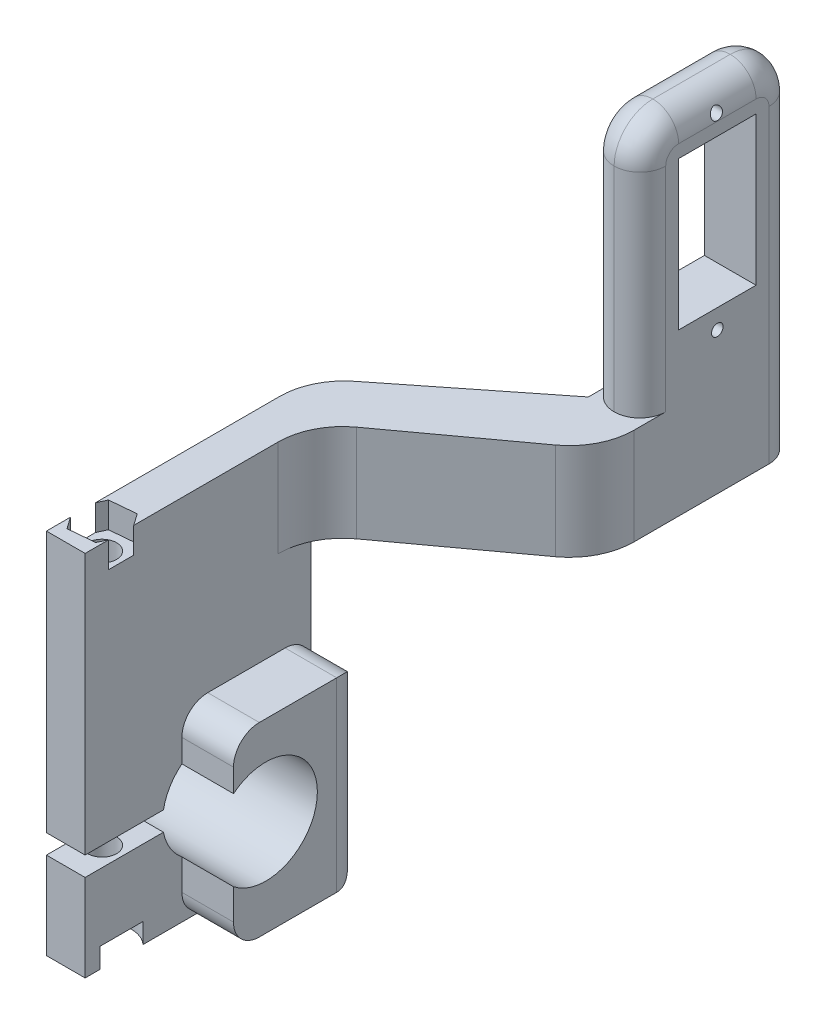
SolidWorks part; units mm, degrees
ref_plane "Front Plane" through (0, 0, 0) normal (0, 0, 1) x (1, 0, 0)
ref_plane "Top Plane" through (0, 0, 0) normal (0, 1, 0) x (1, 0, 0)
ref_plane "Right Plane" through (0, 0, 0) normal (1, 0, 0) x (0, 0, -1)
sketch "Sketch1" plane through (0, 0, 0) normal (1, 0, 0) x (0, 0, -1)
  line L0 (-55.3503, -42.4114) -> (-43.2084, -42.4114)
  line L2 (4.6497, -1.9114) -> (4.6497, 37.0886)
  line L3 (4.6497, 37.0886) -> (28.6497, 37.0886)
  line L4 (10.6497, 31.0886) -> (22.6497, 31.0886)
  line L5 (-27.3711, -35.4334) -> (28.6497, 37.0886) construction
  line L6 (4.6497, 37.0886) -> (-5.2585, -41.9446) construction
  line L7 (-20.3503, -58.9114) -> (-55.3503, -58.9114)
  line L8 (-55.3503, -45.4114) -> (-43.2084, -45.4114)
  line L10 (-55.3503, -58.9114) -> (-55.3503, -45.4114)
  line L11 (10.6497, 31.0886) -> (10.6497, 8.0886)
  line L12 (28.6497, 37.0886) -> (28.6497, -16.9114)
  line L13 (10.6497, 8.0886) -> (22.6497, 8.0886)
  line L14 (22.6497, 31.0886) -> (22.6497, 8.0886)
  line L15 (-55.3503, -42.4114) -> (-55.3503, -28.9114)
  line L18 (28.6497, -16.9114) -> (-20.3503, -16.9114)
  line L19 (4.6497, -1.9114) -> (-55.3503, -1.9114)
  line L20 (-55.3503, -28.9114) -> (-55.3503, -1.9114)
  line L21 (-20.3503, -58.9114) -> (-20.3503, -16.9114)
  arc A0 (-43.2084, -45.4114) -> (-43.2084, -42.4114) centre (-35.3503, -43.9114) ccw
  circle A1 centre (16.6497, 34.0886) radius 0.9
  circle A2 centre (16.6497, 5.0886) radius 0.9
  point P0 (0, 0)
  dimension "D3" = 16
  dimension "D11" = 1.8
  dimension "D12" = 1.8
  dimension "D1" = 30
  dimension "D2" = 15
  dimension "D4" = 35
  dimension "D5" = 20
  dimension "D6" = 24
  dimension "D7" = 12
  dimension "D8" = 6
  dimension "D9" = 6
  dimension "D10" = 23
  dimension "D13" = 3
  dimension "D14" = 3
  dimension "D15" = 6
  dimension "D16" = 6
  dimension "D17" = 13.5
  dimension "D18" = 3
  dimension "D19" = 86
  dimension "D20" = 25
  dimension "D21" = 42
  dimension "D22" = 60
extrude "Boss-Extrude1" add sketch "Sketch1" along normal blind 32
hole_wizard "CBORE for M4 Pan Head Machine Screw2" positions "Sketch6" profile "Sketch5" counterbore size "M4" standard "ANSI Metric" end condition through all
sketch "Sketch6" plane through (0, -58.9114, 0) normal (0, -1, 0) x (-1, 0, 0)
  line L0 (-32, -55.3503) -> (0, -55.3503) construction
  line L1 (0, -55.3503) -> (0, -20.3503) construction
  point P0 (-3, -49.7203)
  dimension "D1" = 5.63
  dimension "D2" = 3
sketch "Sketch5" plane through (3, -58.9114, 49.7203) normal (1, 0, 0) x (0, 0, -1)
  line L0 (0, 0) -> (0, 96)
  line L1 (0, 96) -> (2.25, 96)
  line L3 (2.25, 96) -> (2.25, 3.1)
  line L4 (2.25, 3.1) -> (4.5, 3.1)
  line L5 (4.5, 3.1) -> (4.5, 0)
  line L7 (4.5, 0) -> (0, 0)
  line L11 (0, -6.35) -> (0, 107.95) construction
  dimension "Thru Hole Dia." = 4.5
  dimension "Thru Hole Depth" = 96
  dimension "C'Bore Dia." = 9
  dimension "C'Bore Depth" = 3.1
sketch "Sketch7" plane through (0, -1.9114, 0) normal (0, 1, 0) x (1, 0, 0)
  line L1 (7.0823, -49.3481) -> (4.7188, -45.9989)
  line L2 (4.7188, -45.9989) -> (0.6365, -46.3711)
  line L3 (0.6365, -46.3711) -> (-1.0823, -50.0925)
  line L4 (-1.0823, -50.0925) -> (1.2812, -53.4417)
  line L5 (1.2812, -53.4417) -> (5.3635, -53.0695)
  line L6 (5.3635, -53.0695) -> (7.0823, -49.3481)
  circle A0 centre (3, -49.7203) radius 3.55 construction
  dimension "D1" = 7.1
extrude "Cut-Extrude2" cut sketch "Sketch7" against normal blind 4
sketch "Sketch9" plane through (32, 0, 0) normal (1, 0, 0) x (0, 0, -1)
  line L0 (4.6497, -1.9114) -> (-55.3503, -1.9114) construction
  line L1 (-55.3503, -58.9114) -> (-20.3503, -58.9114)
  line L2 (-55.3503, -58.9114) -> (-55.3503, -1.9114)
  line L3 (-55.3503, -1.9114) -> (-20.3503, -1.9114)
  line L4 (-20.3503, -58.9114) -> (-20.3503, -1.9114)
  line L5 (-20.3503, -58.9114) -> (-20.3503, -16.9114) construction
  dimension "D1" = 0
extrude "Cut-Extrude3" cut sketch "Sketch9" against normal blind 26
sketch "Sketch10" plane through (0, 0, 0) normal (-1, 0, 0) x (0, 0, 1)
  line L1 (-28.6497, -16.9114) -> (-4.6497, -16.9114)
  line L2 (-28.6497, -16.9114) -> (-28.6497, 37.0886)
  line L3 (-28.6497, 37.0886) -> (-4.6497, 37.0886)
  line L4 (-4.6497, -16.9114) -> (-4.6497, 37.0886)
extrude "Cut-Extrude4" cut sketch "Sketch10" against normal blind 24
sketch "Sketch11" plane through (0, 0, 0) normal (-1, 0, 0) x (0, 0, 1)
  line L0 (20.3503, -30.1091) -> (40.3503, -30.1091)
  line L1 (20.3503, -58.9114) -> (20.3503, -16.9114) construction
  line L2 (40.3503, -30.1091) -> (40.3503, -37.6664)
  line L3 (40.3503, -50.1564) -> (40.3503, -58.9114)
  line L4 (46.3662, -58.9114) -> (20.3503, -58.9114) construction
  line L5 (40.3503, -58.9114) -> (20.3503, -58.9114)
  line L6 (20.3503, -58.9114) -> (20.3503, -30.1091)
  arc A0 (40.3503, -37.6664) -> (40.3503, -50.1564) centre (35.3503, -43.9114) ccw
  dimension "D2" = 8
  dimension "D1" = 20
extrude "Boss-Extrude2" add sketch "Sketch11" along normal blind 8 and the other way blind 14
fillet "Fillet3" radius 4 9 edges at (10, -58.9114, 40.3503) (10, -30.1091, 40.3503) (-4, -58.9114, 40.3503) (-4, -30.1091, 40.3503) (10, -30.1091, 20.3503) (14, -44.5103, 20.3503) (3, -58.9114, 20.3503) (-8, -44.5103, 20.3503) (-4, -30.1091, 20.3503)
fillet "Fillet4" radius 6 2 edges at (28, 37.0886, -4.6497) (28, 37.0886, -28.6497)
fillet "Fillet5" radius 4 10 edges at (32, 14.5886, -4.6497) (32, 35.3312, -6.4071) (32, 37.0886, -16.6497) (32, 35.3312, -26.8923) (24, 14.5886, -4.6497) (24, 35.3312, -6.4071) (24, 37.0886, -16.6497) (24, 35.3312, -26.8923) (32, 7.0886, -28.6497) (24, 7.0886, -28.6497)
sketch "Sketch13" plane through (0, -1.9114, 0) normal (0, 1, 0) x (1, 0, 0)
  line L0 (6, -20.3503) -> (32, -1.3503)
  line L1 (32, 8.6497) -> (32, -20.3503) construction
  line L2 (32, -1.3503) -> (32, -20.3503)
  line L3 (32, -20.3503) -> (6, -20.3503)
  line L5 (0, 4.6497) -> (24, 4.6497)
  line L6 (24, 4.6497) -> (0, 4.6497) construction
  line L7 (24, 4.6497) -> (0, -14.3503)
  line L8 (0, 4.6497) -> (0, -47.7493) construction
  line L9 (0, -14.3503) -> (0, 4.6497)
  dimension "D1" = 0
  dimension "D2" = 6
  dimension "D3" = 6
extrude "Cut-Extrude5" cut sketch "Sketch13" against normal through all
fillet "Fillet6" radius 10 3 edges at (0, -9.4114, 14.3503) (32, -9.4114, 1.3503) (6, -9.4114, 20.3503)
